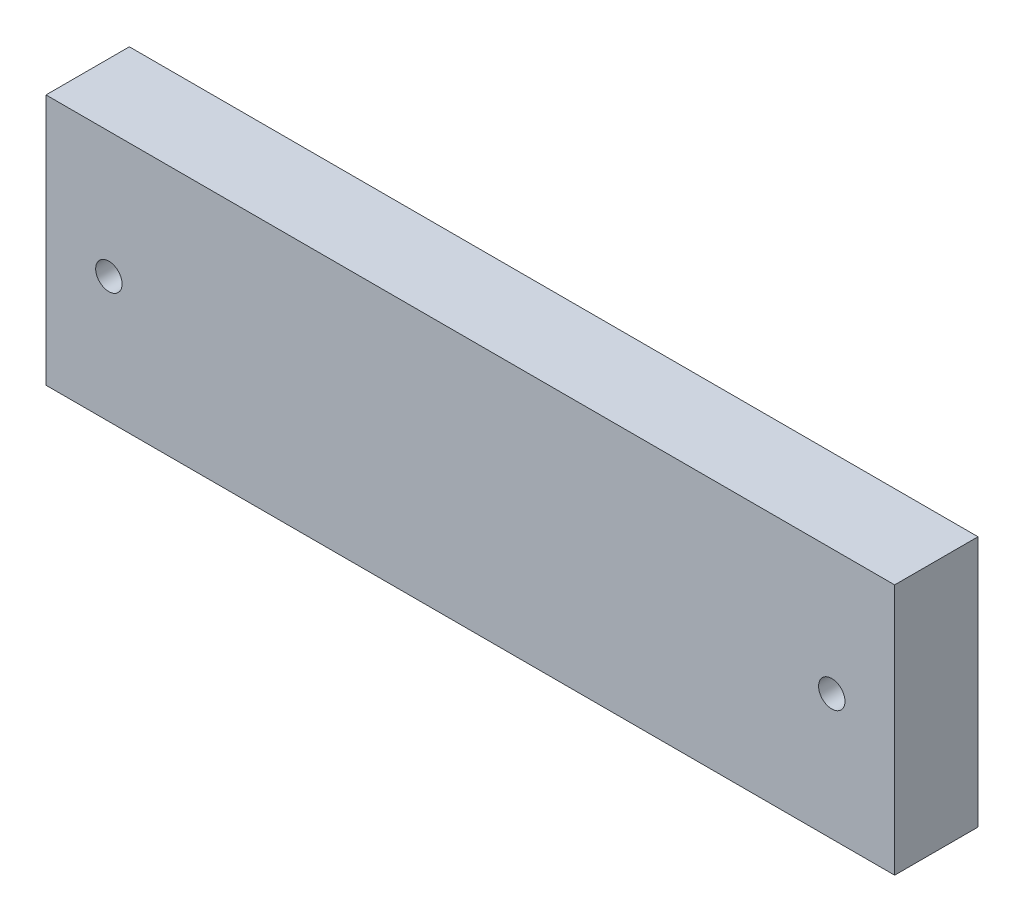
SolidWorks part; units mm, degrees
material "1060 Alloy"
ref_plane "Front Plane" through (0, 0, 0) normal (0, 0, 1) x (1, 0, 0)
ref_plane "Top Plane" through (0, 0, 0) normal (0, 1, 0) x (1, 0, 0)
ref_plane "Right Plane" through (0, 0, 0) normal (1, 0, 0) x (0, 0, -1)
sketch "Sketch1" plane through (0, 0, 0) normal (0, 0, 1) x (1, 0, 0)
  line L1 (-67.5, 20) -> (67.5, 20)
  line L2 (-67.5, 20) -> (-67.5, -20)
  line L3 (-67.5, -20) -> (67.5, -20)
  line L4 (67.5, 20) -> (67.5, -20)
  line L5 (-67.5, 20) -> (67.5, -20) construction
  line L6 (-67.5, -20) -> (67.5, 20) construction
  point P0 (0, 0)
  dimension "D1" = 40
  dimension "D2" = 135
extrude "Boss-Extrude1" add sketch "Sketch1" along normal mid plane 13.26
hole_wizard "M5x0.8 Tapped Hole1" positions "Sketch3" profile "Sketch2" tap size "M5x0.8" standard "ANSI Metric" end condition through all
sketch "Sketch3" plane through (0, 0, 6.63) normal (0, 0, 1) x (1, 0, 0)
  line L0 (-67.5, 20) -> (-67.5, -20) construction
  line L2 (67.5, -20) -> (67.5, 20) construction
  line L3 (67.5, 20) -> (-67.5, 20) construction
  point P0 (57.5, 0)
  point P2 (-57.5, 0)
  point P11 (67.5, 0)
  dimension "D1" = 10
  dimension "D2" = 10
  dimension "D3" = 20
sketch "Sketch2" plane through (57.5, 0, 6.63) normal (1, 0, 0) x (0, -1, 0)
  line L0 (0, 0) -> (0, 13.26)
  line L1 (0, 13.26) -> (2.1, 13.26)
  line L2 (2.1, 13.26) -> (2.1, 0)
  line L5 (2.1, 0) -> (0, 0)
  line L11 (0, -6.35) -> (0, 107.95) construction
  dimension "Thru Tap Drill Dia." = 4.2
  dimension "Thru Tap Drill Depth" = 13.26
cosmetic thread "Hole Thread1" parameters "D2"=5
cosmetic thread "Hole Thread2" parameters "D2"=5
ref_axis "Axis1" through (-57.5, 0, -6.63) along (0, 0, 1)
